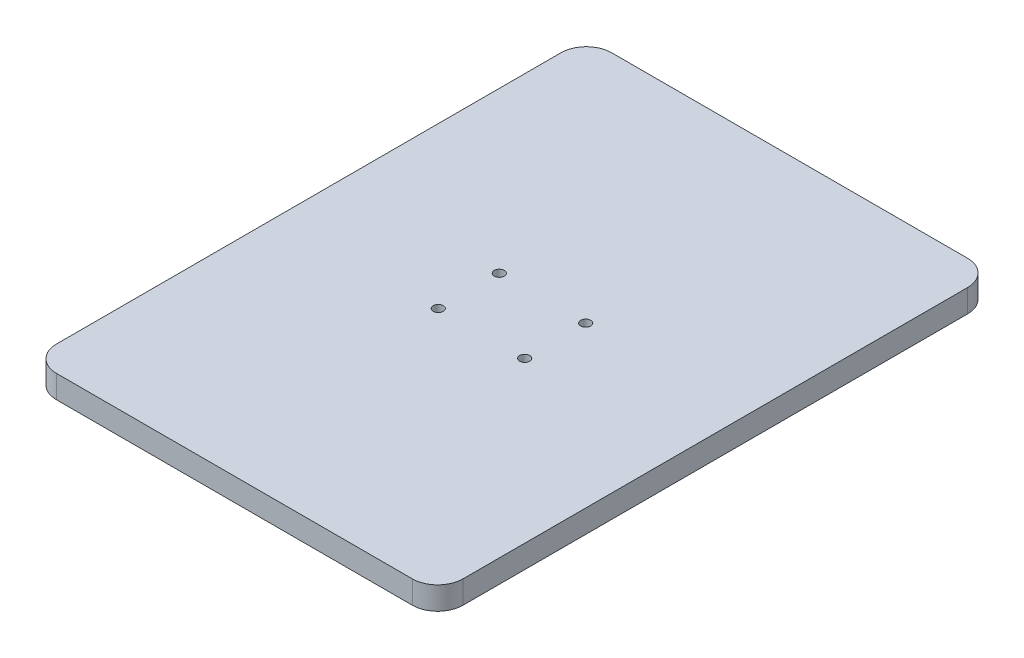
SolidWorks part; units mm, degrees
ref_plane "Front Plane" through (0, 0, 0) normal (0, 0, 1) x (1, 0, 0)
ref_plane "Top Plane" through (0, 0, 0) normal (0, 1, 0) x (1, 0, 0)
ref_plane "Right Plane" through (0, 0, 0) normal (1, 0, 0) x (0, 0, -1)
sketch "Sketch1" plane through (0, 27.05, 0) normal (0, 1, 0) x (1, 0, 0)
  line L0 (0, 69.3699) -> (-12.5, 69.3699) construction
  line L1 (-44.45, -69.3699) -> (44.45, -69.3699)
  line L2 (-50.8, -63.0199) -> (-50.8, 63.0199)
  line L3 (-44.45, 69.3699) -> (44.45, 69.3699)
  line L4 (50.8, -63.0199) -> (50.8, 63.0199)
  line L5 (-50.8, -69.3699) -> (50.8, 69.3699) construction
  line L6 (-50.8, 69.3699) -> (50.8, -69.3699) construction
  arc A0 (44.45, -69.3699) -> (50.8, -63.0199) centre (44.45, -63.0199) ccw
  arc A1 (-44.45, -69.3699) -> (-50.8, -63.0199) centre (-44.45, -63.0199) cw
  arc A2 (-50.8, 63.0199) -> (-44.45, 69.3699) centre (-44.45, 63.0199) cw
  arc A3 (44.45, 69.3699) -> (50.8, 63.0199) centre (44.45, 63.0199) cw
  circle A4 centre (10.795, 7.62) radius 1.25 construction
  circle A5 centre (10.795, -7.62) radius 1.25 construction
  circle A6 centre (-10.795, -7.62) radius 1.25 construction
  circle A7 centre (-10.795, 7.62) radius 1.25 construction
  circle A8 centre (10.795, 7.62) radius 1.25
  circle A9 centre (10.795, -7.62) radius 1.25
  circle A10 centre (-10.795, -7.62) radius 1.25
  circle A11 centre (-10.795, 7.62) radius 1.25
  point P0 (0, 0)
  dimension "D2" = 6.35
  dimension "D1" = 101.6
extrude "Boss-Extrude1" add sketch "Sketch1" along normal blind 5.715
